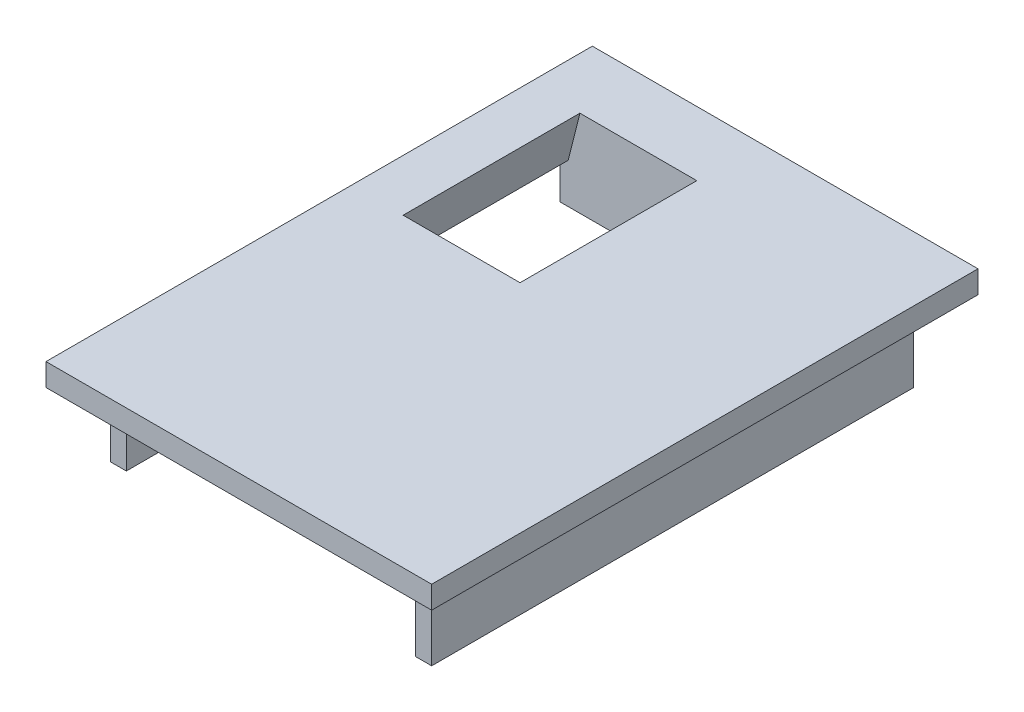
SolidWorks part; units mm, degrees
ref_plane "Płaszczyzna przednia" through (0, 0, 0) normal (0, 0, 1) x (1, 0, 0)
ref_plane "Płaszczyzna górna" through (0, 0, 0) normal (0, 1, 0) x (1, 0, 0)
ref_plane "Płaszczyzna prawa" through (0, 0, 0) normal (1, 0, 0) x (0, 0, -1)
sketch "Szkic1" plane through (0, 0, 0) normal (0, 1, 0) x (1, 0, 0)
  line L1 (-12, -17) -> (12, -17)
  line L2 (-12, -17) -> (-12, 17)
  line L3 (-12, 17) -> (12, 17)
  line L4 (12, -17) -> (12, 17)
  line L5 (-12, -17) -> (12, 17) construction
  line L6 (-12, 17) -> (12, -17) construction
  point P0 (0, 0)
  dimension "D1" = 24
  dimension "D2" = 34
extrude "Dodanie-wyciągnięcie1" add sketch "Szkic1" along normal blind 1.4
sketch "Szkic2" plane through (0, 0, 0) normal (0, -1, 0) x (1, 0, 0)
  line L5 (-8, 13) -> (8, 13)
  line L6 (-10, -15) -> (10, -15)
  line L10 (-10, -15) -> (-10, 15)
  line L11 (-10, 15) -> (10, 15)
  line L12 (10, -15) -> (10, 15)
  line L13 (-10, -15) -> (10, 15) construction
  line L14 (-10, 15) -> (10, -15) construction
  line L15 (8, 13) -> (8, -13)
  line L16 (8, -13) -> (-8, -13)
  line L17 (-8, -13) -> (-8, 13)
  line L18 (-12, 17) -> (12, 17) construction
  line L20 (12, 17) -> (12, -17) construction
  point P0 (0, 0)
  dimension "D2" = 2
  dimension "D3" = 2
  dimension "D4" = 2
  dimension "D5" = 2
  dimension "D6" = 2
  dimension "D7" = 2
extrude "Dodanie-wyciągnięcie2" add sketch "Szkic2" along normal blind 4
sketch "Szkic3" plane through (0, 0, 0) normal (0, -1, 0) x (1, 0, 0)
  line L0 (-8, -13) -> (-4.75, -13) construction
  line L1 (-4.75, -13) -> (-4.75, -7.5) construction
  line L2 (-8, -13) -> (8, -13) construction
  line L3 (-1.5, -13) -> (-8, -13)
  line L4 (-1.5, -13) -> (-1.5, -2)
  line L5 (-1.5, -2) -> (-8, -2)
  line L6 (-8, -13) -> (-8, -2)
  line L7 (-1.5, -13) -> (-8, -2) construction
  line L8 (-1.5, -2) -> (-8, -13) construction
  line L9 (-8, 13) -> (-8, -13) construction
  dimension "D1" = 3.25
  dimension "D2" = 5.5
  dimension "D3" = 11
  dimension "D4" = 6.5
extrude "Wytnij-wyciągnięcie1" cut sketch "Szkic3" against normal through all
sketch "Szkic4" plane through (0, 0, 15) normal (0, 0, 1) x (1, 0, 0)
  line L0 (0, 0) -> (0, -1) construction
  line L1 (-12, 0) -> (12, 0) construction
  line L2 (-9, -1) -> (9, -1)
  line L3 (9, -1) -> (9, -4)
  line L4 (10, -4) -> (-10, -4) construction
  line L5 (9, -4) -> (-9, -4)
  line L6 (-9, -4) -> (-9, -1)
  point P7 (0, -1)
  dimension "D1" = 3
  dimension "D2" = 18
extrude "Wytnij-wyciągnięcie2" cut sketch "Szkic4" against normal up to surface (2 mm away) up to face at (0, -2, 13)
sketch "Szkic5" plane through (-10, 0, 0) normal (-1, 0, 0) x (0, 0, 1)
  line L0 (-15, -4) -> (-13, -4) construction
  line L1 (-15, -4) -> (-15, 0) construction
  line L2 (15, -4) -> (-15, -4) construction
  line L3 (-13, -4) -> (-13, -1.5)
  line L4 (-13, -1.5) -> (-2, -1.5)
  line L5 (-2, -1.5) -> (-2, -4)
  line L6 (-2, -4) -> (-13, -4)
  dimension "D1" = 2
  dimension "D2" = 11
  dimension "D3" = 2.5
extrude "Wytnij-wyciągnięcie3" cut sketch "Szkic5" against normal up to surface (2 mm away) up to face at (-8, -0.8857, 1.2857)
chamfer "Sfazowanie1" distance 1.5 distance2 6 1 edges at (-8, -1.5, -7.5) first distance on face at (-9, -1.5, -7.5)
sketch "Szkic6" plane through (0, -4, 0) normal (0, -1, 0) x (1, 0, 0)
  line L0 (10, -15) -> (10, 15) construction
  line L1 (10, -15) -> (8, -15)
  line L2 (10, -15) -> (10, 13)
  line L3 (9, 13) -> (8, 13)
  line L4 (8, -15) -> (8, 13)
  line L5 (10, -15) -> (8, 13) construction
  line L6 (10, 13) -> (8, -15) construction
  line L7 (-10, -15) -> (10, -15) construction
  line L8 (8, 13) -> (9, 13) construction
  line L9 (8, -13) -> (8, 13) construction
  line L10 (10, 13) -> (10, 15)
  line L11 (10, 15) -> (9, 15) construction
  line L12 (10, 15) -> (9, 15)
  line L13 (9, 15) -> (9, 13)
  line L14 (10, 13) -> (9, 13) construction
  point P4 (9, -1)
extrude "Dodanie-wyciągnięcie3" add sketch "Szkic6" along normal blind 1
